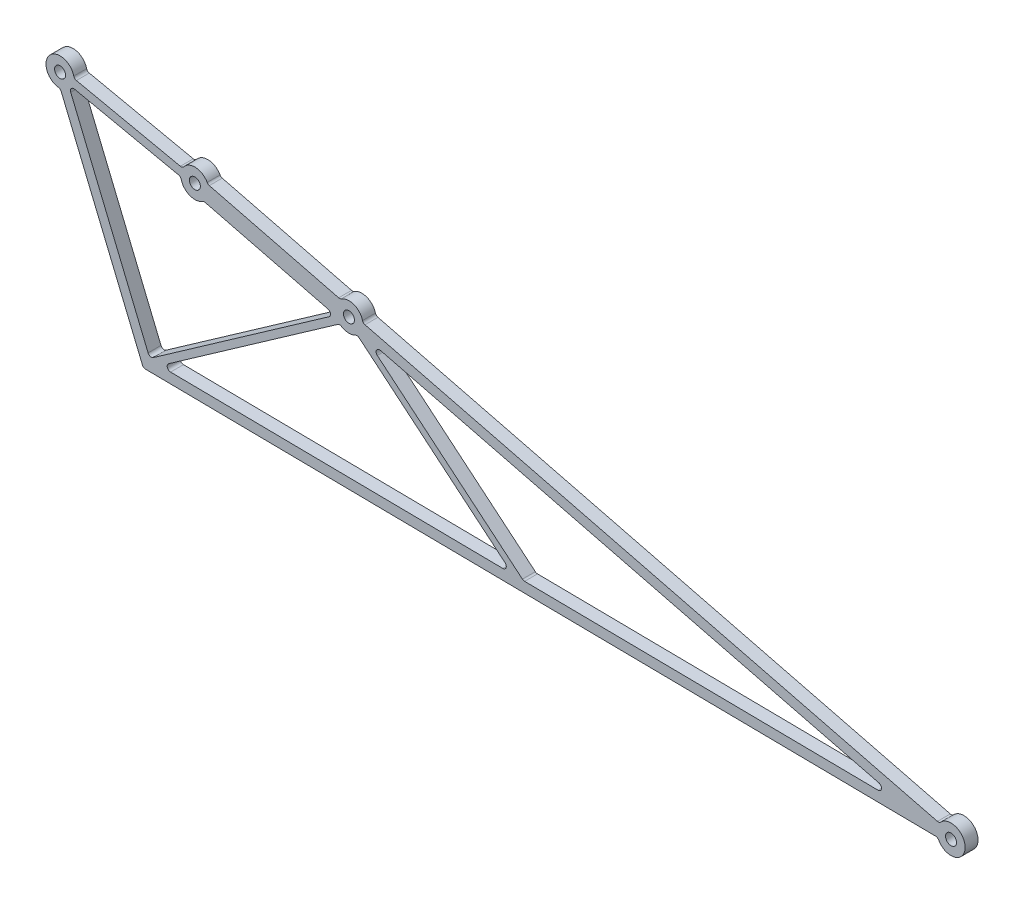
SolidWorks part; units mm, degrees
material "6061-T6 (SS)"
ref_plane "Front Plane" through (0, 0, 0) normal (0, 0, 1) x (1, 0, 0)
ref_plane "Top Plane" through (0, 0, 0) normal (0, 1, 0) x (1, 0, 0)
ref_plane "Right Plane" through (0, 0, 0) normal (1, 0, 0) x (0, 0, -1)
sketch "Sketch1" plane through (0, 0, 0) normal (0, 0, 1) x (1, 0, 0)
  line L9 (-668.1664, 18.6436) -> (-87.8384, -105.5749)
  line L10 (-555.71, 150.418) -> (2.5386, 10.0998)
  line L12 (-556.069, 150.5014) -> (-655.5727, 171.8001)
  line L16 (7.4774, -7.2484) -> (-87.8384, -105.5749)
  line L18 (-668.1664, 18.6436) -> (-668.1664, 161.6168)
  circle A2 centre (-558.2487, 140.3181) radius 4.064
  circle A5 centre (0, 0) radius 4.064
  circle A6 centre (-444.5, 111.7269) radius 4.064
  circle A7 centre (-657.7524, 161.6168) radius 4.064
  circle A8 centre (0, 0) radius 10.414
  circle A9 centre (-558.2487, 140.3181) radius 10.414
  circle A10 centre (-657.7524, 161.6168) radius 10.414
  circle A11 centre (-444.5, 111.7269) radius 10.414
  dimension "D4" = 60
  dimension "D7" = 6.35
  dimension "D10" = 140.3181
  dimension "D19" = 8.128
  dimension "D2" = 152.4
  dimension "D3" = 444.5
  dimension "D6" = 558.2487
  dimension "D11" = 657.7524
  dimension "D12" = 161.6168
extrude "Boss-Extrude1" add sketch "Sketch1" along normal mid plane 9.525 contours A10 A7 | A9 A2 | A11 A6 | A8 A5 | A11 A9 A10 A8 region at (-436.5198, 117.9495, 0) region at (-357.2288, 26.9003, 0) region at (-664.1152, 169.4856, 0) region at (-9.7327, -2.7707, 0) region at (-555.9559, 150.1744, 0)
sketch3d "3DSketch1"
  line L0 (-444.5, 111.7269, 4.7625) -> (-444.5, 111.7269, -4.7625) construction
  line L1 (-444.5, 111.7269, -4.7625) -> (-444.5, 111.7269, -14.2875) construction
  line L2 (-444.5, 111.7269, 4.7625) -> (-444.5, 111.7269, 14.2875) construction
  circle A0 centre (-444.5, 111.7269, 4.7625) radius 4.064 construction
  circle A1 centre (-444.5, 111.7269, -4.7625) radius 4.064 construction
  circle A2 centre (-444.5, 111.7269, 4.7625) radius 4.064
  circle A3 centre (-444.5, 111.7269, -4.7625) radius 4.064
  point P2 (-444.5, 111.7269, 8.8265)
  point P5 (-444.5, 111.7269, -0.6985)
  point P7 (-444.5, 111.7269, 8.8265)
  point P9 (-444.5, 111.7269, -0.6985)
sketch "Sketch3" plane through (0, 0, 0) normal (0, 0, 1) x (1, 0, 0)
  line L0 (-555.71, 150.418) -> (2.5386, 10.0998) construction
  line L1 (7.4774, -7.2484) -> (-87.8384, -105.5749) construction
  line L2 (-668.1664, 18.6436) -> (-87.8384, -105.5749) construction
  line L3 (-668.1664, 18.6436) -> (-668.1664, 161.6168) construction
  line L4 (-556.069, 150.5014) -> (-655.5727, 171.8001) construction
  line L5 (-555.71, 150.418) -> (2.5386, 10.0998)
  line L6 (7.4774, -7.2484) -> (-87.8384, -105.5749)
  line L7 (-668.1664, 18.6436) -> (-87.8384, -105.5749)
  line L8 (-668.1664, 18.6436) -> (-668.1664, 161.6168)
  line L9 (-556.069, 150.5014) -> (-655.5727, 171.8001)
  line L10 (0, 0) -> (-444.5, 111.7269) construction
  line L11 (-444.5, 111.7269) -> (-558.2487, 140.3181) construction
  line L12 (-558.2487, 140.3181) -> (-657.7524, 161.6168) construction
  line L13 (-450.9571, 119.8974) -> (-548.6957, 144.4645)
  line L14 (-451.3103, 103.8484) -> (-584.0724, 10.741)
  line L15 (-593.7651, 7.0457) -> (-657.7524, 161.6168) construction
  line L17 (-593.7651, 7.0457) -> (0, 0) construction
  line L18 (-568.6118, 139.2894) -> (-648.7184, 156.4361)
  line L19 (-591.5647, 11.6913) -> (-650.525, 154.119)
  line L20 (-443.0416, 109.6473) -> (-592.3067, 4.9662) construction
  line L21 (-596.3239, 3.2658) -> (-9.7365, -3.6947)
  line L22 (-8.4709, 6.0577) -> (-434.1716, 113.0593)
  line L24 (-596.3239, 3.2658) -> (-657.5656, 151.2045)
  line L26 (-584.0724, 10.741) -> (-32.3139, 4.1937)
  line L27 (-32.3139, 4.1937) -> (-436.0291, 105.6692)
  line L29 (-454.053, 107.5806) -> (-551.7916, 132.1476)
  line L30 (-597.2854, 5.5884) -> (-661.2727, 160.1595) construction
  line L31 (-445.2611, 115.8467) -> (-605.6329, 3.3763) construction
  line L32 (-605.6329, 3.3763) -> (32.3139, -4.1937) construction
  line L34 (-590.2448, 8.503) -> (-654.2321, 163.0741) construction
  line L35 (-443.7389, 107.6071) -> (-581.8973, 10.7152) construction
  line L37 (-32.3139, 4.1937) -> (-443.7389, 107.6071) construction
  line L38 (32.3139, -4.1937) -> (-445.2611, 115.8467) construction
  line L39 (-567.2826, 145.4987) -> (-647.3893, 162.6455)
  line L40 (-558.9132, 137.2134) -> (-658.4169, 158.5121) construction
  line L41 (-444.5, 111.7269) -> (-593.7651, 7.0457) construction
  line L42 (-557.5841, 143.4228) -> (-657.0878, 164.7214) construction
  line L43 (-446.0479, 105.5685) -> (-559.7966, 134.1597) construction
  line L44 (-442.9521, 117.8854) -> (-556.7007, 146.4766) construction
  line L45 (-454.6294, 107.7255) -> (-591.5647, 11.6913)
  line L47 (-444.5, 111.7269) -> (-502.0697, 71.3527) construction
  line L49 (-445.9584, 113.8065) -> (-503.5281, 73.4323) construction
  line L50 (-444.5, 111.7269) -> (-593.7651, 7.0457) construction
  line L51 (-436.5047, 105.0541) -> (-319.74, 7.6044) construction
  line L52 (-438.3736, 103.3056) -> (-323.7613, 7.6521)
  line L53 (-435.1186, 107.2057) -> (-315.7187, 7.5566)
  line L54 (-437.3168, 109.0403) -> (-318.1125, 9.5544) construction
  line L55 (-440.5718, 105.1402) -> (-321.3675, 5.6543) construction
  line L56 (-438.9443, 107.0902) -> (-319.74, 7.6044) construction
  line L58 (-581.8973, 10.7152) -> (-32.3139, 4.1937) construction
  circle A0 centre (-657.7524, 161.6168) radius 4.064 construction
  circle A1 centre (-558.2487, 140.3181) radius 4.064 construction
  circle A2 centre (-444.5, 111.7269) radius 4.064 construction
  circle A3 centre (0, 0) radius 4.064 construction
  arc A4 (7.4774, -7.2484) -> (2.5386, 10.0998) centre (0, 0) ccw construction
  arc A5 (-655.5727, 171.8001) -> (-668.1664, 161.6168) centre (-657.7524, 161.6168) ccw construction
  circle A6 centre (-657.7524, 161.6168) radius 4.064
  circle A7 centre (-558.2487, 140.3181) radius 4.064
  circle A8 centre (-444.5, 111.7269) radius 4.064
  circle A9 centre (0, 0) radius 4.064
  arc A10 (7.4774, -7.2484) -> (2.5386, 10.0998) centre (0, 0) ccw
  arc A11 (-655.5727, 171.8001) -> (-668.1664, 161.6168) centre (-657.7524, 161.6168) ccw
  circle A12 centre (-558.2487, 140.3181) radius 10.414
  circle A13 centre (-444.5, 111.7269) radius 10.414
  circle A14 centre (-657.7524, 161.6168) radius 10.414
  circle A15 centre (0, 0) radius 10.414
  point P35 (-561.3534, 140.9827)
  point P36 (-590.3355, 5.5829)
  point P42 (-555.144, 139.6536)
  point P43 (-584.1262, 4.2538)
  point P72 (-443.0263, 108.9147)
  point P73 (-659.908, 159.2857)
  point P74 (-595.7964, 28.8561)
  point P75 (-477.2272, 91.8774)
  point P76 (-656.2614, 163.6731)
  point P84 (-560.5551, 141.3821)
  point P87 (-475.3766, 93.1752)
  point P90 (-620.2928, 11.8934)
  point P92 (-555.9423, 139.2541)
  point P94 (-615.68, 9.7654)
  dimension "D1" = 6.35
  dimension "D2" = 3.175
  dimension "D3" = 3.81
  dimension "D4" = 3.81
  dimension "D5" = 3.175
  dimension "D6" = 6.35
  dimension "D7" = 6.35
  dimension "D8" = 2.54
  dimension "D9" = 2.54
  dimension "D10" = 2.54
  dimension "D11" = 2.54
extrude "Cut-Extrude2" cut sketch "Sketch3" along direction (0, 0, -1) on the side against the normal through all both and the other way through all contours A14 L8 L7 L24 | A14 L39 A12 L9 | A15 L21 L7 L6 | A13 L5 L13 | L27 L53 L26 | A13 L14 L26 L52 | A14 L19 L45 L29 A12 L18 | A15 L5 A13 L22 region at (-499.3211, 134.1913, 0) region at (-220.5119, 62.7785, 0) region at (-606.5569, 157.7118, 0) region at (-566.2534, 92.5256, 0) region at (-643.8117, 64.3263, 0) region at (-225.1705, -35.5028, 0) region at (-450.8469, 42.0578, 0) region at (-260.0414, 38.81, 0)
fillet "Fillet5" radius 2.54 22 edges at (-9.7365, -3.6947, 0) (-8.4709, 6.0577, 0) (-32.3139, 4.1937, 0) (-315.7187, 7.5566, 0) (-323.7613, 7.6521, 0) (-451.3103, 103.8484, 0) (-438.3736, 103.3056, 0) (-432.0917, 104.6795, 0) (-454.6294, 107.7255, 0) (-434.1716, 113.0593, 0) (-450.9571, 119.8974, 0) (-551.7916, 132.1476, 0) (-568.6118, 139.2894, 0) (-548.6957, 144.4645, 0) (-567.2826, 145.4987, 0) (-584.0724, 10.741, 0) (-591.5647, 11.6913, 0) (-596.3239, 3.2658, 0) (-657.5656, 151.2045, 0) (-650.525, 154.119, 0) (-648.7184, 156.4361, 0) (-647.3893, 162.6455, 0)
